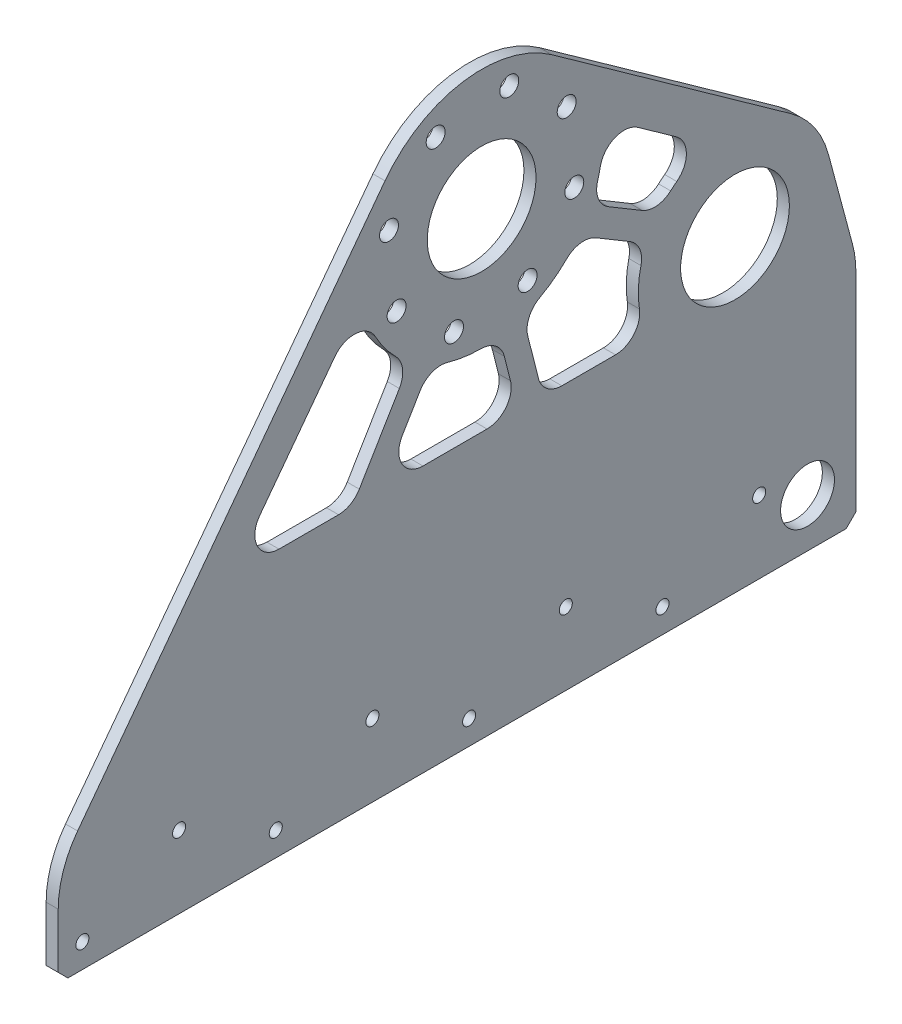
SolidWorks part; units mm, degrees
material "6061-T6 (SS)"
ref_plane "Front Plane" through (0, 0, 0) normal (0, 0, 1) x (1, 0, 0)
ref_plane "Top Plane" through (0, 0, 0) normal (0, 1, 0) x (1, 0, 0)
ref_plane "Right Plane" through (0, 0, 0) normal (1, 0, 0) x (0, 0, -1)
sketch "Sketch1" plane through (0, 0, 0) normal (1, 0, 0) x (0, 0, -1)
  line L0 (0, -25.4) -> (0, 31.864)
  line L13 (-209.55, -25.4) -> (0, -25.4)
  line L14 (-209.55, -25.4) -> (-209.55, -8.4756)
  line L15 (-204.4603, 6.7773) -> (-123.6994, 114.3161)
  line L16 (-209.55, 0) -> (0, 0) construction
  line L17 (-7.2155, 62.1365) -> (-0.8655, 38.438)
  line L18 (-79.8716, 121.0963) -> (-16.9981, 76.2396)
  circle A5 centre (-31.75, 55.5625) radius 14.2875
  circle A6 centre (-98.3115, 95.25) radius 14.2875 construction
  arc A7 (-79.8716, 121.0963) -> (-123.6994, 114.3161) centre (-98.3115, 95.25) ccw
  arc A8 (-16.9981, 76.2396) -> (-7.2155, 62.1365) centre (-31.75, 55.5625) cw
  circle A9 centre (-98.3115, 95.25) radius 14.2875
  arc A10 (-209.55, -8.4756) -> (-204.4603, 6.7773) centre (-184.15, -8.4756) cw
  arc A11 (-0.8655, 38.438) -> (0, 31.864) centre (-25.4, 31.864) cw
  point P4 (0, 0)
  dimension "D4" = 31.75
  dimension "D7" = 25.4
  dimension "D10" = 28.575
  dimension "D3" = 41.275
  dimension "D9" = 25.4
  dimension "D12" = 77.4954
  dimension "D13" = 63.5
  dimension "D14" = 63.5
  dimension "D5" = 25.4
  dimension "D8" = 28.575
  dimension "D2" = 15
  dimension "D6" = 209.55
extrude "Boss-Extrude1" add sketch "Sketch1" along normal blind 3.175
hole_wizard "#10 Clearance Hole1" positions "Sketch2" profile "Sketch3" hole size "#10" standard "ANSI Inch" end condition through all
sketch "Sketch2" plane through (3.175, 0, 0) normal (1, 0, 0) x (0, 0, -1)
  line L0 (-98.3115, 95.25) -> (-31.75, 55.5625) construction
  line L1 (-72.9115, 95.25) -> (-86.2351, 72.9046) construction
  circle A0 centre (-98.3115, 95.25) radius 25.4 construction
  circle A1 centre (-31.75, 55.5625) radius 14.2875 construction
  point P17 (-91.0503, 119.59)
  point P38 (-75.9661, 107.3265)
  point P39 (-73.9716, 87.9887)
  point P40 (-86.2351, 72.9046)
  point P41 (-105.5728, 70.91)
  point P42 (-120.657, 83.1735)
  point P43 (-122.6515, 102.5113)
  point P44 (-110.388, 117.5954)
  dimension "D1" = 50.8
  dimension "D2" = 8
sketch "Sketch3" plane through (3.175, 119.59, 91.0503) normal (0, 1, 0) x (0, 0, -1)
  line L0 (0, 0) -> (0, 3.175)
  line L1 (0, 3.175) -> (2.4892, 3.175)
  line L2 (2.4892, 3.175) -> (2.4892, 0)
  line L5 (2.4892, 0) -> (0, 0)
  line L11 (0, -6.35) -> (0, 107.95) construction
  dimension "Thru Hole Dia." = 4.9784
  dimension "Thru Hole Depth" = 3.175
sketch "Sketch9" plane through (3.175, 0, 0) normal (1, 0, 0) x (0, 0, -1)
  line L0 (0, 0) -> (-208.0942, 0) construction
  line L1 (0, -25.4) -> (0, 31.864) construction
  line L2 (0, -25.4) -> (0, 31.864) construction
  line L3 (-209.55, -25.4) -> (0, -25.4) construction
  line L4 (-164.2565, 44.45) -> (-129.699, 90.4657)
  line L5 (-123.6994, 114.3161) -> (-204.4603, 6.7773) construction
  line L6 (-176.1684, 44.45) -> (-132.2977, 44.45) construction
  line L7 (-164.2565, 44.45) -> (-132.2977, 44.45)
  line L8 (-66.9456, 100.1737) -> (-38.6711, 80.0014)
  line L9 (-16.9981, 76.2396) -> (-79.8716, 121.0963) construction
  line L10 (-69.5519, 81.7985) -> (-51.7692, 71.1955)
  line L11 (-55.0212, 65.7415) -> (-72.8039, 76.3444)
  line L12 (-98.3115, 95.25) -> (-31.75, 55.5625) construction
  line L13 (-98.3115, 95.25) -> (-132.7027, 37.5711) construction
  line L14 (-98.3115, 95.25) -> (-81.8784, 30.2801) construction
  line L15 (-117.2171, 69.7423) -> (-132.2977, 44.45)
  line L16 (-124.9046, 44.45) -> (-111.763, 66.4903)
  line L17 (-93.6431, 63.8451) -> (-88.7375, 44.45)
  line L18 (-82.1875, 44.45) -> (-87.487, 65.4022)
  line L19 (-82.1875, 44.45) -> (0, 44.45) construction
  line L20 (-82.1875, 44.45) -> (-54.5901, 44.45)
  line L21 (-124.9046, 44.45) -> (-88.7375, 44.45) construction
  line L22 (-124.9046, 44.45) -> (-88.7375, 44.45)
  circle A0 centre (-12.7, -12.7) radius 7.0739
  arc A2 (-204.4603, 6.7773) -> (-209.55, -8.4756) centre (-184.15, -8.4756) ccw construction
  arc A3 (-69.5519, 81.7985) -> (-117.2171, 69.7423) centre (-98.3115, 95.25) ccw construction
  arc A4 (-79.8716, 121.0963) -> (-123.6994, 114.3161) centre (-98.3115, 95.25) ccw construction
  arc A5 (-55.0212, 65.7415) -> (-51.7692, 71.1955) centre (-31.75, 55.5625) ccw construction
  arc A6 (-7.2155, 62.1365) -> (-16.9981, 76.2396) centre (-31.75, 55.5625) ccw construction
  arc A7 (-129.699, 90.4657) -> (-117.2171, 69.7423) centre (-98.3115, 95.25) ccw
  arc A8 (-54.5901, 44.45) -> (-55.0212, 65.7415) centre (-31.75, 55.5625) cw
  arc A9 (-51.7692, 71.1955) -> (-38.6711, 80.0014) centre (-31.75, 55.5625) cw
  arc A10 (-69.5519, 81.7985) -> (-66.9456, 100.1737) centre (-98.3115, 95.25) ccw
  arc A11 (-87.487, 65.4022) -> (-72.8039, 76.3444) centre (-98.3115, 95.25) ccw construction
  arc A12 (-87.487, 65.4022) -> (-72.8039, 76.3444) centre (-98.3115, 95.25) ccw
  arc A13 (-111.763, 66.4903) -> (-93.6431, 63.8451) centre (-98.3115, 95.25) ccw construction
  arc A14 (-111.763, 66.4903) -> (-93.6431, 63.8451) centre (-98.3115, 95.25) ccw
  dimension "D1" = 14.1478
  dimension "D3" = 12.7
  dimension "D2" = 12.7
  dimension "D4" = 9.525
  dimension "D5" = 44.45
  dimension "D6" = 9.525
  dimension "D7" = 6.35
  dimension "D8" = 6.35
  dimension "D9" = 6.35
  dimension "D10" = 45
  dimension "D11" = 45
extrude "Cut-Extrude1" cut sketch "Sketch9" against normal through all
fillet "Fillet1" radius 6.35 17 edges at (1.5875, 100.1737, 66.9456) (1.5875, 71.1955, 51.7692) (1.5875, 81.7985, 69.5519) (1.5875, 80.0014, 38.6711) (1.5875, 76.3444, 72.8039) (1.5875, 65.7415, 55.0212) (1.5875, 44.45, 82.1875) (1.5875, 65.4022, 87.487) (1.5875, 44.45, 54.5901) (1.5875, 44.45, 124.9046) (1.5875, 66.4903, 111.763) (1.5875, 63.8451, 93.6431) (1.5875, 44.45, 88.7375) (1.5875, 44.45, 164.2565) (1.5875, 90.4657, 129.699) (1.5875, 69.7423, 117.2171) (1.5875, 44.45, 132.2977)
hole_wizard "1/8 (0.135) Diameter Hole1" positions "Sketch10" profile "Sketch11" hole size "1/8" standard "ANSI Inch" end condition through all
sketch "Sketch10" plane through (3.175, 0, 0) normal (1, 0, 0) x (0, 0, -1)
  point P4 (-177.8, -6.35)
  point P7 (-152.4, -19.05)
  point P10 (-127, -6.35)
  point P13 (-101.6, -19.05)
  point P16 (-76.2, -6.35)
  point P19 (-50.8, -19.05)
  point P22 (-25.4, -6.35)
  point P26 (-203.2, -19.05)
sketch "Sketch11" plane through (3.175, -6.35, 177.8) normal (0, 1, 0) x (0, 0, -1)
  line L0 (0, 0) -> (0, 3.175)
  line L1 (0, 3.175) -> (1.7145, 3.175)
  line L2 (1.7145, 3.175) -> (1.7145, 0)
  line L5 (1.7145, 0) -> (0, 0)
  line L11 (0, -6.35) -> (0, 107.95) construction
  dimension "Thru Hole Dia." = 3.429
  dimension "Thru Hole Depth" = 3.175
chamfer "Chamfer1" distance 2.54 angle 45 2 edges at (1.5875, -25.4, 0) (1.5875, -25.4, 209.55)
